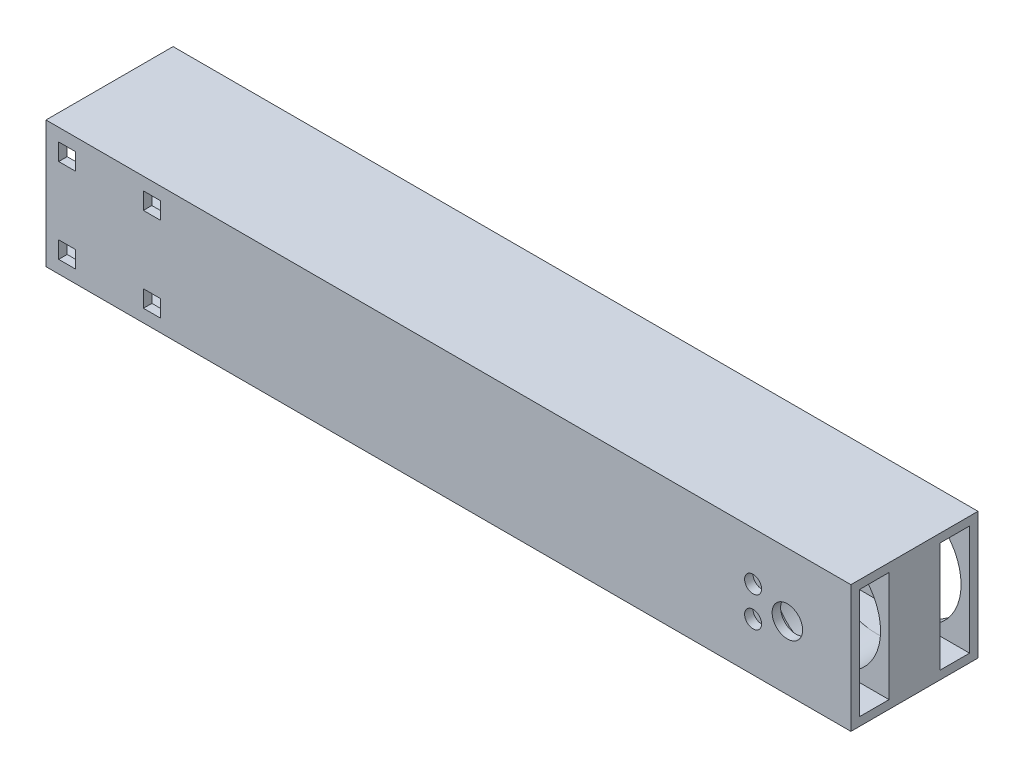
SolidWorks part; units mm, degrees
material "PLA 15%"
ref_plane "Front Plane" through (0, 0, 0) normal (0, 0, 1) x (1, 0, 0)
ref_plane "Top Plane" through (0, 0, 0) normal (0, 1, 0) x (1, 0, 0)
ref_plane "Right Plane" through (0, 0, 0) normal (1, 0, 0) x (0, 0, -1)
sketch "Sketch1" plane through (0, 0, 0) normal (1, 0, 0) x (0, 0, -1)
  line L1 (-15, -15) -> (15, -15)
  line L2 (-15, -15) -> (-15, 15)
  line L3 (-15, 15) -> (15, 15)
  line L4 (15, -15) -> (15, 15)
  line L5 (-15, -15) -> (15, 15) construction
  line L6 (-15, 15) -> (15, -15) construction
  line L11 (-5.1844, 5.1844) -> (5.1844, -5.1844) construction
  line L12 (-5.1844, -5.1844) -> (5.1844, 5.1844) construction
  line L13 (-13, 13) -> (-6, 13)
  line L14 (-13, 13) -> (-13, -13)
  line L15 (-13, -13) -> (-6, -13)
  line L16 (-6, 13) -> (-6, -13)
  line L17 (13, 13) -> (6, 13)
  line L18 (13, 13) -> (13, -13)
  line L19 (13, -13) -> (6, -13)
  line L20 (6, 13) -> (6, -13)
  point P0 (0, 0)
  point P7 (0, 0)
  dimension "D1" = 30
  dimension "D2" = 30
  dimension "D3" = 2
  dimension "D4" = 7
  dimension "D5" = 2
  dimension "D6" = 7
  dimension "D7" = 2
  dimension "D8" = 2
extrude "Boss-Extrude3" add sketch "Sketch1" along normal blind 110 and the other way blind 80
sketch "Sketch6" plane through (0, 0, -15) normal (0, 0, -1) x (-1, 0, 0)
  line L0 (-110, -15) -> (-110, 15) construction
  line L2 (-110, 0) -> (80, 0) construction
  line L3 (80, -15) -> (80, 15) construction
  circle A0 centre (-95, 0) radius 13
  dimension "D2" = 26
  dimension "D1" = 15
extrude "Cut-Extrude5" cut sketch "Sketch6" against normal blind 23
sketch "Sketch8" plane through (0, 0, 15) normal (0, 0, 1) x (1, 0, 0)
  line L0 (110, 15) -> (110, -15) construction
  circle A0 centre (95, 0) radius 3.6
  circle A1 centre (86.9069, 3.5812) radius 2
  circle A2 centre (86.9069, -3.5812) radius 2
  dimension "D2" = 7.2
  dimension "D5" = 4
  dimension "D6" = 4
  dimension "D1" = 15
  dimension "D3" = 8.85
  dimension "D4" = 8.85
extrude "Cut-Extrude6" cut sketch "Sketch8" against normal blind 17
sketch "Sketch9" plane through (-80, 0, 0) normal (-1, 0, 0) x (0, 0, 1)
  line L0 (-6, 13) -> (6, 13)
  line L1 (-6, -13) -> (6, -13)
  line L2 (-6, 13) -> (-6, -13)
  line L3 (6, 13) -> (6, -13)
extrude "Cut-Extrude7" cut sketch "Sketch9" against normal blind 106
sketch "Sketch12" plane through (0, 0, 15) normal (0, 0, 1) x (1, 0, 0)
  line L0 (-80, 15) -> (110, 15) construction
  line L1 (-80, 15) -> (-80, -15) construction
  line L2 (-80, 15) -> (-50, 15) construction
  line L3 (-50, 15) -> (-50, -15) construction
  line L5 (-80, -15) -> (110, -15) construction
  line L6 (-77, 8) -> (-73, 8)
  line L7 (-77, 8) -> (-77, 12)
  line L8 (-77, 12) -> (-73, 12)
  line L9 (-73, 8) -> (-73, 12)
  line L10 (-77, 8) -> (-73, 12) construction
  line L11 (-77, 12) -> (-73, 8) construction
  line L12 (-57.0136, 8) -> (-52.9864, 8)
  line L13 (-57.0136, 8) -> (-57.0136, 12)
  line L14 (-57.0136, 12) -> (-52.9864, 12)
  line L15 (-52.9864, 8) -> (-52.9864, 12)
  line L16 (-57.0136, 8) -> (-52.9864, 12) construction
  line L17 (-57.0136, 12) -> (-52.9864, 8) construction
  line L18 (-57, -12) -> (-53, -12)
  line L19 (-57, -12) -> (-57, -8)
  line L20 (-57, -8) -> (-53, -8)
  line L21 (-53, -12) -> (-53, -8)
  line L22 (-57, -12) -> (-53, -8) construction
  line L23 (-57, -8) -> (-53, -12) construction
  line L24 (-77, -12) -> (-73, -12)
  line L25 (-77, -12) -> (-77, -8)
  line L26 (-77, -8) -> (-73, -8)
  line L27 (-73, -12) -> (-73, -8)
  line L28 (-77, -12) -> (-73, -8) construction
  line L29 (-77, -8) -> (-73, -12) construction
  circle A2 centre (-55, 10) radius 2
  circle A3 centre (-75, -10) radius 2
  circle A4 centre (-55, -10) radius 2
  dimension "D3" = 4
  dimension "D7" = 4
  dimension "D9" = 4
  dimension "D11" = 4
  dimension "D2" = 4
  dimension "D4" = 5
  dimension "D5" = 30
  dimension "D6" = 5
  dimension "D8" = 5
  dimension "D10" = 5
  dimension "D12" = 20
  dimension "D13" = 5
  dimension "D14" = 4
extrude "Cut-Extrude8" cut sketch "Sketch12" against normal blind 40 contours L8 L9 L6 L7 | L14 L15 L12 L13 | L20 L21 L18 L19 | L26 L27 L24 L25
